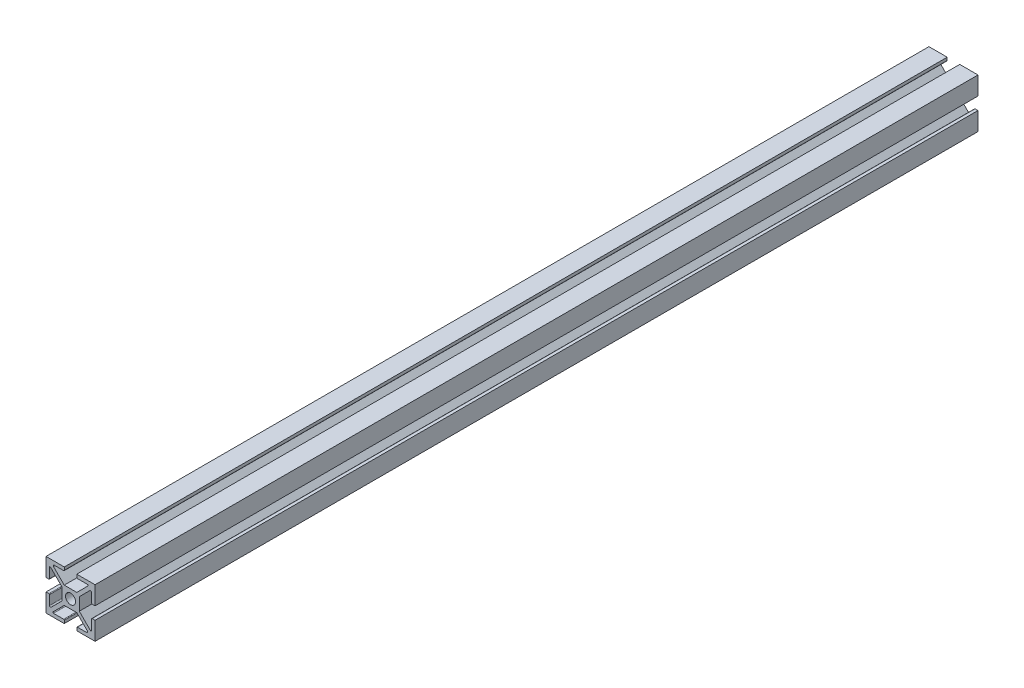
SolidWorks part; units mm, degrees
ref_plane "Front Plane" through (0, 0, 0) normal (0, 0, 1) x (1, 0, 0)
ref_plane "Top Plane" through (0, 0, 0) normal (0, 1, 0) x (1, 0, 0)
ref_plane "Right Plane" through (0, 0, 0) normal (1, 0, 0) x (0, 0, -1)
sketch "Sketch2" plane through (0, 0, 0) normal (0, 0, 1) x (1, 0, 0)
  line L1 (-12.7, -12.7) -> (12.7, -12.7)
  line L2 (-12.7, -12.7) -> (-12.7, 12.7)
  line L3 (-12.7, 12.7) -> (12.7, 12.7)
  line L4 (12.7, -12.7) -> (12.7, 12.7)
  line L5 (-12.7, -12.7) -> (12.7, 12.7) construction
  line L6 (-12.7, 12.7) -> (12.7, -12.7) construction
  point P0 (0, 0)
  dimension "D1" = 25.4
  dimension "D2" = 25.4
extrude "Boss-Extrude2" add sketch "Sketch2" along normal blind 457.2
sketch "Sketch3" plane through (0, 0, 457.2) normal (0, 0, 1) x (1, 0, 0)
  line L0 (-3.2385, 12.7) -> (-3.2385, 11.2075)
  line L1 (12.7, 12.7) -> (-12.7, 12.7) construction
  line L2 (-3.5572, 10.8887) -> (-8.3814, 10.8887)
  line L3 (-8.7406, 10.0215) -> (-3.2597, 4.5406)
  line L4 (-3.2597, 4.5406) -> (3.2597, 4.5406)
  line L5 (-3.2385, 12.7) -> (3.2385, 12.7)
  line L6 (0, -1000) -> (0, 49000) construction
  line L7 (9.0637, 10.3446) -> (3.2597, 4.5406)
  line L8 (3.5572, 10.8887) -> (8.8383, 10.8887)
  line L9 (3.2385, 12.7) -> (3.2385, 11.2075)
  line L10 (12.7, 3.2385) -> (11.2075, 3.2385)
  line L11 (10.8887, 3.5572) -> (10.8887, 8.3814)
  line L12 (10.0215, 8.7406) -> (4.5406, 3.2597)
  line L13 (4.5406, 3.2597) -> (4.5406, -3.2597)
  line L14 (12.7, 3.2385) -> (12.7, -3.2385)
  line L15 (10.3446, -9.0637) -> (4.5406, -3.2597)
  line L16 (10.8887, -3.5572) -> (10.8887, -8.8383)
  line L17 (12.7, -3.2385) -> (11.2075, -3.2385)
  line L18 (3.2385, -12.7) -> (3.2385, -11.2075)
  line L19 (3.5572, -10.8887) -> (8.3814, -10.8887)
  line L20 (8.7406, -10.0215) -> (3.2597, -4.5406)
  line L21 (3.2597, -4.5406) -> (-3.2597, -4.5406)
  line L22 (3.2385, -12.7) -> (-3.2385, -12.7)
  line L23 (-9.0637, -10.3446) -> (-3.2597, -4.5406)
  line L24 (-3.5572, -10.8887) -> (-8.8383, -10.8887)
  line L25 (-3.2385, -12.7) -> (-3.2385, -11.2075)
  line L26 (-12.7, -3.2385) -> (-11.2075, -3.2385)
  line L27 (-10.8887, -3.5572) -> (-10.8887, -8.3814)
  line L28 (-10.0215, -8.7406) -> (-4.5406, -3.2597)
  line L29 (-4.5406, -3.2597) -> (-4.5406, 3.2597)
  line L30 (-12.7, -3.2385) -> (-12.7, 3.2385)
  line L31 (-10.3446, 9.0637) -> (-4.5406, 3.2597)
  line L32 (-10.8887, 3.5572) -> (-10.8887, 8.8383)
  line L33 (-12.7, 3.2385) -> (-11.2075, 3.2385)
  circle A0 centre (0, 0) radius 2.6035
  arc A1 (-8.3814, 10.8887) -> (-8.7406, 10.0215) centre (-8.3814, 10.3807) ccw
  arc A2 (10.8887, 8.3814) -> (10.0215, 8.7406) centre (10.3807, 8.3814) ccw
  arc A3 (10.3446, -9.0637) -> (10.8887, -8.8383) centre (10.57, -8.8383) ccw
  arc A4 (9.0637, 10.3446) -> (8.8383, 10.8887) centre (8.8383, 10.57) ccw
  arc A5 (3.5572, 10.8887) -> (3.2385, 11.2075) centre (3.5572, 11.2075) cw
  arc A6 (-3.2385, 11.2075) -> (-3.5572, 10.8887) centre (-3.5572, 11.2075) cw
  arc A7 (10.8887, -3.5572) -> (11.2075, -3.2385) centre (11.2075, -3.5572) cw
  arc A8 (11.2075, 3.2385) -> (10.8887, 3.5572) centre (11.2075, 3.5572) cw
  arc A9 (8.3814, -10.8887) -> (8.7406, -10.0215) centre (8.3814, -10.3807) ccw
  arc A10 (-9.0637, -10.3446) -> (-8.8383, -10.8887) centre (-8.8383, -10.57) ccw
  arc A11 (-3.5572, -10.8887) -> (-3.2385, -11.2075) centre (-3.5572, -11.2075) cw
  arc A12 (3.2385, -11.2075) -> (3.5572, -10.8887) centre (3.5572, -11.2075) cw
  arc A13 (-10.8887, -8.3814) -> (-10.0215, -8.7406) centre (-10.3807, -8.3814) ccw
  arc A14 (-10.3446, 9.0637) -> (-10.8887, 8.8383) centre (-10.57, 8.8383) ccw
  arc A15 (-10.8887, 3.5572) -> (-11.2075, 3.2385) centre (-11.2075, 3.5572) cw
  arc A16 (-11.2075, -3.2385) -> (-10.8887, -3.5572) centre (-11.2075, -3.5572) cw
  point P12 (0, 12.7)
  point P13 (0, 4.5406)
  point P19 (-9.6078, 10.8887)
  point P20 (3.2597, 4.5406)
  point P22 (-3.2597, 4.5406)
  point P25 (3.2597, 4.5406)
  point P28 (9.6078, 10.8887)
  point P31 (3.2385, 10.8887)
  point P34 (-3.2385, 10.8887)
  point P36 (-3.2597, 4.5406)
  point P42 (12.7, 0)
  point P43 (4.5406, 0)
  point P60 (0, -12.7)
  point P61 (0, -4.5406)
  point P78 (-12.7, 0)
  point P79 (-4.5406, 0)
  dimension "D2" = 5.207
  dimension "D3" = 0.508
  dimension "D5" = 4
  dimension "D1" = 6.477
  dimension "D4" = 135
extrude "Cut-Extrude2" cut sketch "Sketch3" against normal through all
